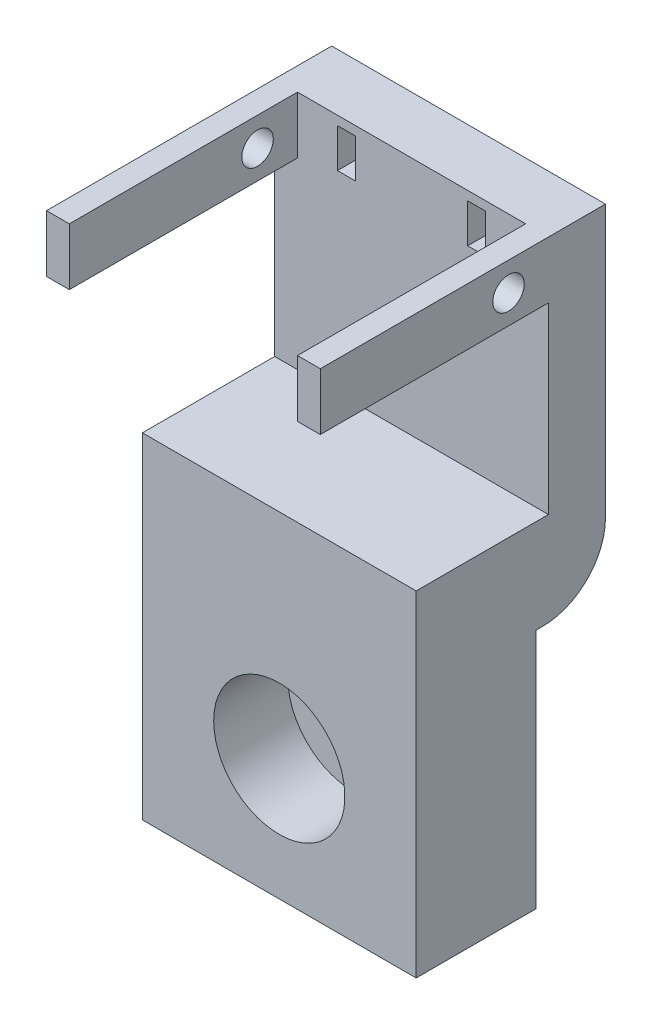
SolidWorks part; units mm, degrees
ref_plane "Front Plane" through (0, 0, 0) normal (0, 0, 1) x (1, 0, 0)
ref_plane "Top Plane" through (0, 0, 0) normal (0, 1, 0) x (1, 0, 0)
ref_plane "Right Plane" through (0, 0, 0) normal (1, 0, 0) x (0, 0, -1)
sketch "Sketch1" plane through (0, 0, 0) normal (0, 0, 1) x (1, 0, 0)
  line L1 (0, 0) -> (48, 0)
  line L2 (0, 0) -> (0, 53)
  line L3 (0, 53) -> (48, 53)
  line L4 (48, 0) -> (48, 53)
  dimension "D1" = 53
  dimension "D2" = 48
extrude "Boss-Extrude1" add sketch "Sketch1" along normal blind 10
sketch "Sketch2" plane through (0, 0, 0) normal (0, 0, -1) x (-1, 0, 0)
  line L0 (0, 53) -> (0, 0) construction
  line L1 (-48, 0) -> (0, 0)
  line L2 (-48, 0) -> (-48, -5.6163)
  line L3 (-48, -5.6163) -> (0, -5.6163)
  line L4 (0, 0) -> (0, -5.6163)
  dimension "D1" = 5.6163
extrude "Boss-Extrude2" add sketch "Sketch2" against normal blind 33.1918
sketch "Sketch4" plane through (0, 0, 10) normal (0, 0, 1) x (1, 0, 0)
  line L1 (0, 53) -> (4, 53)
  line L2 (0, 53) -> (0, 43)
  line L3 (0, 43) -> (4, 43)
  line L4 (4, 53) -> (4, 43)
  line L5 (48, 53) -> (44, 53)
  line L6 (48, 53) -> (48, 43)
  line L7 (48, 43) -> (44, 43)
  line L8 (44, 53) -> (44, 43)
  dimension "D1" = 10
  dimension "D2" = 4
extrude "Boss-Extrude4" add sketch "Sketch4" along normal blind 40
sketch "Sketch5" plane through (0, 0, 10) normal (0, 0, 1) x (1, 0, 0)
  line L0 (48, 0) -> (48, 43) construction
  line L1 (0, 0) -> (48, 0)
  line L2 (0, 0) -> (0, 10.8609)
  line L3 (0, 10.8609) -> (48, 10.8609)
  line L4 (48, 0) -> (48, 10.8609)
  dimension "D1" = 10.8609
extrude "Boss-Extrude5" add sketch "Sketch5" along normal up to surface (23.1918 mm away) up to face at (24, -2.8082, 33.1918)
sketch "Sketch6" plane through (0, -5.6163, 0) normal (0, -1, 0) x (1, 0, 0)
  line L0 (0, 0) -> (0, 28.1918) construction
  line L1 (0, 33.1918) -> (0, 0) construction
  line L2 (48, 33.1918) -> (48, 0) construction
  line L3 (0, 28.1918) -> (48, 28.1918)
  line L4 (0, 28.1918) -> (0, 33.1918)
  line L5 (0, 33.1918) -> (48, 33.1918)
  line L6 (48, 28.1918) -> (48, 33.1918)
  line L8 (48, 33.1918) -> (0, 33.1918) construction
  dimension "D2" = 5
extrude "Boss-Extrude6" add sketch "Sketch6" along normal blind 42.3
sketch "Sketch8" plane through (0, 0, 28.1918) normal (0, 0, -1) x (-1, 0, 0)
  line L0 (-24, -26.6163) -> (-24, -5.6163) construction
  line L1 (0, -5.6163) -> (-48, -5.6163) construction
  line L3 (-8.5, -42.1163) -> (-39.5, -42.1163) construction
  line L4 (-8.5, -42.1163) -> (-8.5, -11.1163) construction
  line L5 (-8.5, -11.1163) -> (-39.5, -11.1163) construction
  line L6 (-39.5, -42.1163) -> (-39.5, -11.1163) construction
  line L7 (-8.5, -42.1163) -> (-39.5, -11.1163) construction
  line L8 (-8.5, -11.1163) -> (-39.5, -42.1163) construction
  circle A0 centre (-24, -26.6163) radius 11.5
  circle A1 centre (-39.5, -11.1163) radius 2 construction
  circle A2 centre (-39.5, -42.1163) radius 2 construction
  circle A3 centre (-8.5, -11.1163) radius 2 construction
  circle A4 centre (-8.5, -42.1163) radius 2 construction
  dimension "D2" = 23
  dimension "D4" = 4
  dimension "D1" = 21
  dimension "D3" = 31
extrude "Cut-Extrude1" cut sketch "Sketch8" against normal up to next
sketch "Sketch9" plane through (48, 0, 0) normal (1, 0, 0) x (0, 0, -1)
  line L0 (0, -5.6163) -> (0, 53) construction
  line L1 (-50, 43) -> (-17, 48) construction
  line L2 (-17, 48) -> (-50, 53) construction
  circle A0 centre (-17, 48) radius 2.7623
  dimension "D1" = 5.5245
  dimension "D2" = 17
extrude "Cut-Extrude2" cut sketch "Sketch9" against normal through all
sketch "Sketch10" plane through (0, 0, 0) normal (0, 0, -1) x (-1, 0, 0)
  line L0 (-48, 53) -> (-37, 51.4163) construction
  line L1 (-37, 51.4163) -> (-33.8453, 51.4163)
  line L2 (-37, 51.4163) -> (-37, 44.5837)
  line L3 (-37, 44.5837) -> (-33.8453, 44.5837)
  line L4 (-33.8453, 51.4163) -> (-33.8453, 44.5837)
  line L5 (-14.1547, 51.4163) -> (-11, 51.4163)
  line L6 (-14.1547, 51.4163) -> (-14.1547, 44.5837)
  line L7 (-14.1547, 44.5837) -> (-11, 44.5837)
  line L8 (-11, 51.4163) -> (-11, 44.5837)
  line L9 (0, 53) -> (-11, 51.4163) construction
  line L10 (-48, 53) -> (0, 53) construction
  dimension "D1" = 3.1547
  dimension "D2" = 1.5837
  dimension "D3" = 6.8326
  dimension "D4" = 19.6906
extrude "Cut-Extrude3" cut sketch "Sketch10" against normal up to next
sketch "Sketch11" plane through (0, 0, 28.1918) normal (0, 0, -1) x (-1, 0, 0)
  line L1 (-48, -5.6163) -> (0, -5.6163)
  line L2 (-48, -5.6163) -> (-48, -47.9163)
  line L3 (-48, -47.9163) -> (0, -47.9163)
  line L4 (0, -5.6163) -> (0, -47.9163)
  circle A0 centre (-24, -26.6163) radius 11.5
  circle A1 centre (-24, -26.6163) radius 11.5 construction
extrude "Boss-Extrude7" add sketch "Sketch11" along normal blind 8
sketch "Sketch12" plane through (0, 0, 20.1918) normal (0, 0, -1) x (-1, 0, 0)
  line L1 (-48, -5.6163) -> (0, -5.6163)
  line L2 (-48, -5.6163) -> (-48, -47.9163)
  line L3 (-48, -47.9163) -> (0, -47.9163)
  line L4 (0, -5.6163) -> (0, -47.9163)
extrude "Boss-Extrude8" add sketch "Sketch12" along normal blind 8
fillet "Fillet1" radius 11 1 edges at (24, -5.6163, 0)
